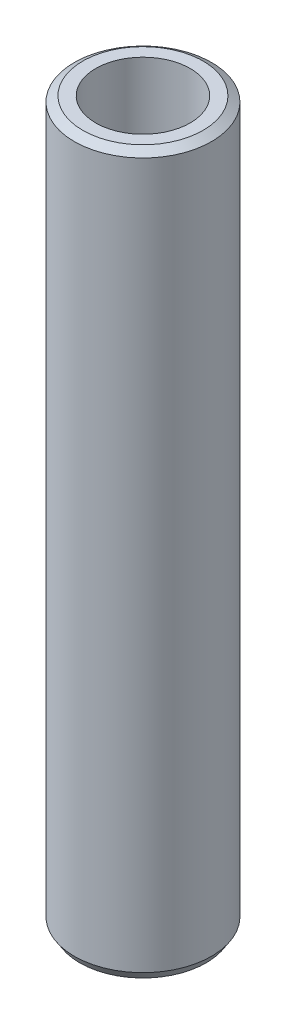
SolidWorks part; units mm, degrees
ref_plane "Front Plane" through (0, 0, 0) normal (0, 0, 1) x (1, 0, 0)
ref_plane "Top Plane" through (0, 0, 0) normal (0, 1, 0) x (1, 0, 0)
ref_plane "Right Plane" through (0, 0, 0) normal (1, 0, 0) x (0, 0, -1)
sketch "Sketch1" plane through (0, 0, 0) normal (0, 1, 0) x (1, 0, 0)
  circle A0 centre (0, 0) radius 47.5
  dimension "SHAFT_OD" = 95
extrude "Boss-Extrude1" add sketch "Sketch1" along normal blind 498.1583
sketch "Sketch2" plane through (0, 0, 0) normal (0, 1, 0) x (1, 0, 0)
  circle A0 centre (0, 0) radius 32.7022
  dimension "BORE_D" = 65.4044
extrude "Cut-Extrude1" cut sketch "Sketch2" along normal through all
chamfer "Chamfer1" distance 3.7745 angle 57.296 2 edges at (0, 498.1583, 47.5) (0, 0, 47.5) first distance on face at (0, 498.1583, 47.5) first distance on face at (0, 0, 32.7022)
